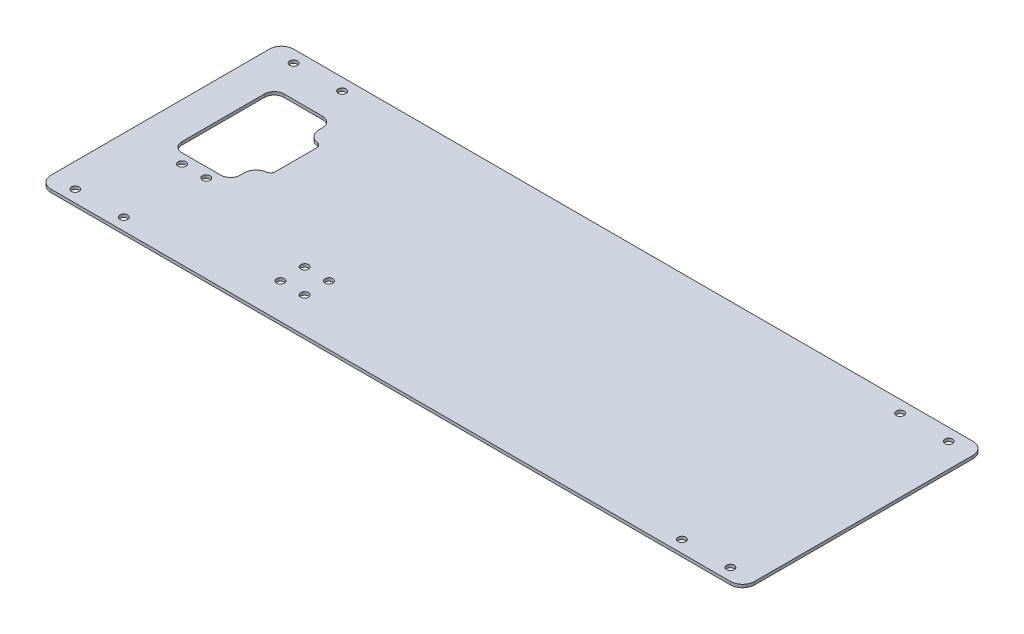
SolidWorks part; units mm, degrees
ref_plane "Front Plane" through (0, 0, 0) normal (0, 0, 1) x (1, 0, 0)
ref_plane "Top Plane" through (0, 0, 0) normal (0, 1, 0) x (1, 0, 0)
ref_plane "Right Plane" through (0, 0, 0) normal (1, 0, 0) x (0, 0, -1)
sketch "Sketch1" plane through (0, 0, 0) normal (0, 1, 0) x (1, 0, 0)
  line L0 (128.27, 0) -> (-128.27, 0) construction
  line L1 (184.15, 63.5) -> (-184.15, 63.5)
  line L2 (184.15, 63.5) -> (184.15, -63.5)
  line L3 (184.15, -63.5) -> (-184.15, -63.5)
  line L4 (-184.15, 63.5) -> (-184.15, -63.5)
  line L5 (184.15, 63.5) -> (-184.15, -63.5) construction
  line L6 (184.15, -63.5) -> (-184.15, 63.5) construction
  line L7 (-128.27, 0) -> (-128.27, 31.75) construction
  line L8 (-128.27, 31.75) -> (-134.62, 31.75) construction
  line L9 (-128.27, 6.35) -> (-134.62, 6.35) construction
  line L12 (-165.1, -12.7) -> (-165.1, 40.64)
  line L15 (-134.62, -12.7) -> (-165.1, -12.7)
  line L17 (-134.62, 40.64) -> (-165.1, 40.64)
  line L18 (0, 63.5) -> (0, -63.5) construction
  line L19 (-134.62, 40.64) -> (-134.62, -12.7)
  line L21 (-76.2, -45.0215) -> (-76.2, -32.3215) construction
  line L22 (-63.5, -45.0215) -> (-76.2, -45.0215) construction
  line L25 (128.27, 31.75) -> (128.27, 6.35) construction
  line L26 (-76.2, -32.3215) -> (-63.5, -32.3215) construction
  line L30 (-63.5, -32.3215) -> (-63.5, -45.0215) construction
  line L31 (184.15, -17.78) -> (154.94, -17.78) construction
  line L32 (146.05, 57.15) -> (184.15, 57.15) construction
  line L33 (154.94, -17.78) -> (142.24, -17.78) construction
  line L34 (146.05, -57.15) -> (184.15, -57.15) construction
  line L35 (-146.05, -57.15) -> (-184.15, -57.15) construction
  line L36 (-146.05, 57.15) -> (-184.15, 57.15) construction
  line L37 (-128.27, 0) -> (-128.27, 6.35) construction
  line L38 (-184.15, -17.78) -> (-154.94, -17.78) construction
  line L39 (-154.94, -17.78) -> (-142.24, -17.78) construction
  line L40 (-134.62, 27.305) -> (-127, 27.305)
  line L41 (-127, 27.305) -> (-127, 0.635)
  line L42 (-127, 0.635) -> (-134.62, 0.635)
  circle A4 centre (171.45, 31.75) radius 2.032 construction
  circle A5 centre (128.27, 31.75) radius 2.032 construction
  circle A6 centre (128.27, 6.35) radius 2.032 construction
  circle A7 centre (171.45, -3.81) radius 2.032 construction
  circle A8 centre (171.45, -57.15) radius 2.032
  circle A9 centre (146.05, -57.15) radius 2.032
  circle A10 centre (171.45, 57.15) radius 2.032
  circle A11 centre (146.05, 57.15) radius 2.032
  circle A12 centre (-146.05, -57.15) radius 2.032
  circle A13 centre (-171.45, -57.15) radius 2.032
  circle A14 centre (-146.05, 57.15) radius 2.032
  circle A15 centre (-171.45, 57.15) radius 2.032
  circle A16 centre (142.24, -17.78) radius 2.032 construction
  circle A17 centre (154.94, -17.78) radius 2.032 construction
  circle A18 centre (-154.94, -17.78) radius 2.032
  circle A19 centre (-142.24, -17.78) radius 2.032
  circle A20 centre (-76.2, -45.0215) radius 2.032
  circle A21 centre (-63.5, -45.0215) radius 2.032
  circle A22 centre (-76.2, -32.3215) radius 2.032
  circle A23 centre (-63.5, -32.3215) radius 2.032
  point P0 (0, 0)
  point P11 (-128.27, 0)
  point P13 (-134.62, 31.75)
  point P17 (-134.62, 6.35)
  point P37 (0, 0)
  point P50 (171.45, 57.15)
  point P51 (146.05, 57.15)
  point P56 (171.45, -57.15)
  point P57 (146.05, -57.15)
  point P84 (-130.81, 27.305)
  point P87 (130.81, 27.305)
  dimension "D5" = 13.335
  dimension "D18" = 4.064
  dimension "D1" = 368.3
  dimension "D2" = 127
  dimension "D3" = 128.27
  dimension "D4" = 25.4
  dimension "D7" = 6.35
  dimension "D8" = 30.48
  dimension "D9" = 53.34
  dimension "D10" = 8.89
  dimension "D11" = 19.05
  dimension "D14" = 12.7
  dimension "D15" = 38.1
  dimension "D16" = 12.7
  dimension "D17" = 38.1
  dimension "D19" = 31.75
  dimension "D20" = 6.35
  dimension "D21" = 6.35
  dimension "D22" = 5.08
  dimension "D23" = 29.21
  dimension "D24" = 12.7
  dimension "D25" = 107.95
  dimension "D26" = 12.7
  dimension "D27" = 7.62
  dimension "D28" = 26.67
  dimension "D29" = 13.335
  dimension "D30" = 18.4785
  dimension "D31" = 12.7
extrude "Boss-Extrude1" add sketch "Sketch1" along normal blind 1.5875 contours L1 L4 L3 L2 A18 A17 A16 A14 A12 A11 A10 A9 A8 L41 L42 L19 L15 L12 L17 L40 A13 A15 A19 region at (6.2039, 0, 0.5157)
sketch "Sketch2" [suppressed] plane through (0, 1.5875, 0) normal (0, 1, 0) x (1, 0, 0)
  line L0 (-69.85, 63.5) -> (-69.85, -63.5)
  line L1 (184.15, 63.5) -> (-184.15, 63.5) construction
  line L2 (184.15, -63.5) -> (-184.15, -63.5) construction
  circle A0 centre (-82.55, -45.0215) radius 2.032 construction
  circle M9 centre (146.05, 57.15) radius 2.032
  circle M10 centre (171.45, 57.15) radius 2.032
  circle M11 centre (146.05, -57.15) radius 2.032
  circle M12 centre (171.45, -57.15) radius 2.032
  line M13 (184.15, 63.5) -> (-184.15, 63.5)
  line M15 (-184.15, -63.5) -> (184.15, -63.5)
  line M16 (184.15, -63.5) -> (184.15, 63.5)
  dimension "D1" = 12.7
extrude "Cut-Extrude1" [suppressed] cut sketch "Sketch2" against normal through all flip side to cut contours L0 M13 M15 M16 M10 M12 M11 M9
fillet "Fillet1" radius 5.08 4 edges at (-134.62, 0.7937, 12.7) (-165.1, 0.7937, 12.7) (-165.1, 0.7937, -40.64) (-134.62, 0.7937, -40.64)
fillet "Fillet3" radius 6.35 4 edges at (184.15, 0.7937, 63.5) (184.15, 0.7937, -63.5) (-184.15, 0.7937, 63.5) (-184.15, 0.7937, -63.5)
fillet "Fillet4" radius 2.54 2 edges at (-127, 0.7937, -0.635) (-127, 0.7937, -27.305)
fillet "Fillet5" radius 6.35 2 edges at (-134.62, 0.7937, -0.635) (-134.62, 0.7937, -27.305)
fillet "Fillet6" [suppressed] radius 6.35
equation "\".80.55in\"=0.55"
